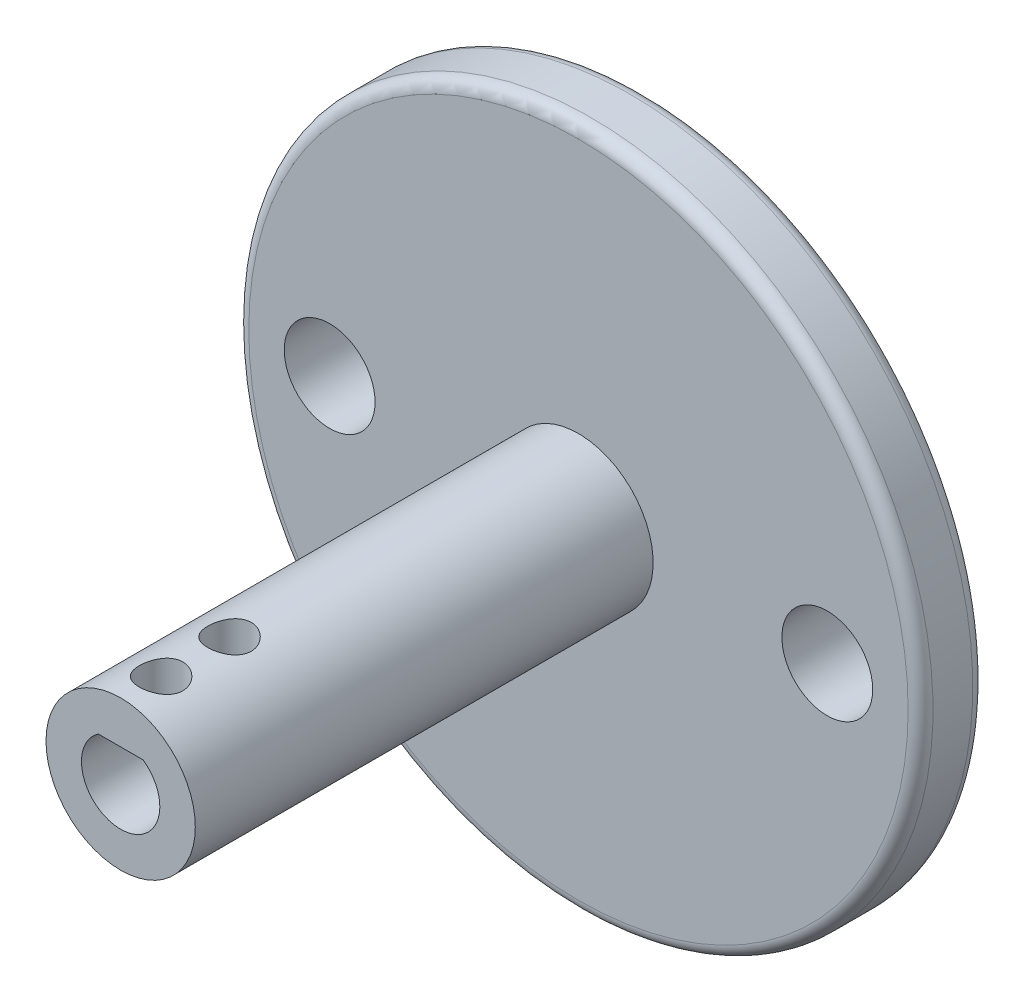
SolidWorks part; units mm, degrees
ref_plane "Alzado" through (0, 0, 0) normal (0, 0, 1) x (1, 0, 0)
ref_plane "Planta" through (0, 0, 0) normal (0, 1, 0) x (1, 0, 0)
ref_plane "Vista lateral" through (0, 0, 0) normal (1, 0, 0) x (0, 0, -1)
sketch "Croquis1" plane through (0, 0, 0) normal (0, 0, 1) x (1, 0, 0)
  line L0 (0, 0) -> (0, 2.5851) construction
  line L7 (-1.8, 2.5851) -> (1.8, 2.5851)
  circle A0 centre (0, 0) radius 6
  arc A1 (-1.8, 2.5851) -> (1.8, 2.5851) centre (0, 0) ccw
  point P14 (0, 2.5851)
  dimension "D2" = 6.3
  dimension "D1" = 12
  dimension "D3" = 3.6
extrude "Saliente-Extruir1" add sketch "Croquis1" along normal blind 40
sketch "Croquis2" plane through (0, 2.5851, 0) normal (0, 1, 0) x (1, 0, 0)
  line L0 (0, -40) -> (0, -36.75) construction
  line L2 (0, -36.75) -> (0, -35) construction
  line L3 (0, -35) -> (0, -33) construction
  line L4 (0, -33) -> (0, -31.25) construction
  line L5 (0, -31.25) -> (0, -28) construction
  line L6 (-6, -40) -> (6, -40) construction
  circle A0 centre (0, -36.75) radius 1.75
  circle A1 centre (0, -31.25) radius 1.75
  point P2 (0, 0)
  point P9 (0, 0)
  dimension "D1" = 3.5
  dimension "D2" = 12
  dimension "D3" = 2
extrude "Cortar-Extruir1" cut sketch "Croquis2" along normal blind 7.5
sketch "Croquis3" plane through (0, 0, 0) normal (0, 0, -1) x (-1, 0, 0)
  circle A0 centre (0, 0) radius 27.5
  point P3 (0, 0)
  dimension "D1" = 55
extrude "Saliente-Extruir2" add sketch "Croquis3" against normal blind 3.2 and the other way blind 2
sketch "Croquis5" plane through (0, 0, -2) normal (0, 0, -1) x (-1, 0, 0)
  line L0 (0, 0) -> (0, 7.5) construction
  line L1 (0, 7.5) -> (-7.5, 7.5) construction
  line L2 (0, 0) -> (-20, 0) construction
  circle A4 centre (-20, 0) radius 3.65
  circle A5 centre (0, 0) radius 27.5
  circle A6 centre (0, 0) radius 27.5
  circle A7 centre (20, 0) radius 3.65
  point P14 (0, 0)
  dimension "D8" = 7.3
  dimension "D1" = 7.5
  dimension "D2" = 7.5
  dimension "D7" = 20
  dimension "D6" = 0
extrude "Cortar-Extruir2" cut sketch "Croquis5" against normal blind 5.2 and the other way through all contours A4 | A7
fillet "Redondeo1" radius 1 2 edges at (-27.5, 0, -2) (-27.5, 0, 3.2)
